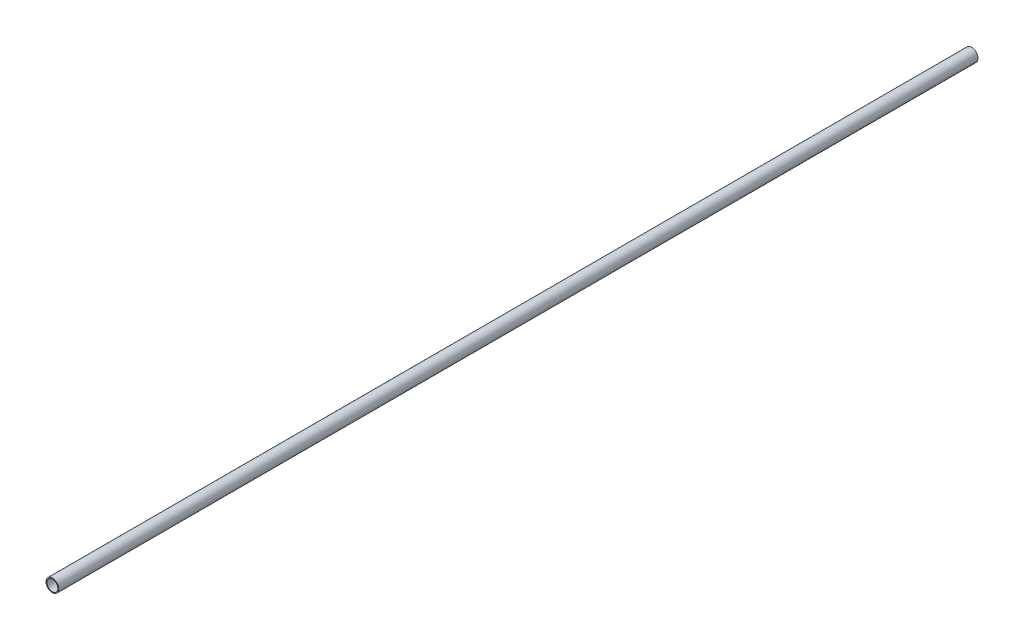
SolidWorks part; units mm, degrees
ref_plane "Front Plane" through (0, 0, 0) normal (0, 0, 1) x (1, 0, 0)
ref_plane "Top Plane" through (0, 0, 0) normal (0, 1, 0) x (1, 0, 0)
ref_plane "Right Plane" through (0, 0, 0) normal (1, 0, 0) x (0, 0, -1)
sketch "Sketch1" plane through (0, 0, 0) normal (0, 0, 1) x (1, 0, 0)
  circle A0 centre (0, 0) radius 6.35
  circle A1 centre (0, 0) radius 5.461
  dimension "D2" = 10.922
extrude "Boss-Extrude1" add sketch "Sketch1" along normal blind 457.2 and the other way blind 457.2
equation "\"pipe_od\"=0.5"
equation "\"D1@Sketch1\"=\"pipe_od\""
equation "\"pipe_id\"=0.43"
equation "\"D2@Sketch1\"=\"pipe_id\""
equation "\"half length\"= 18"
equation "\"D1@Boss-Extrude1\"=\"half length\""
